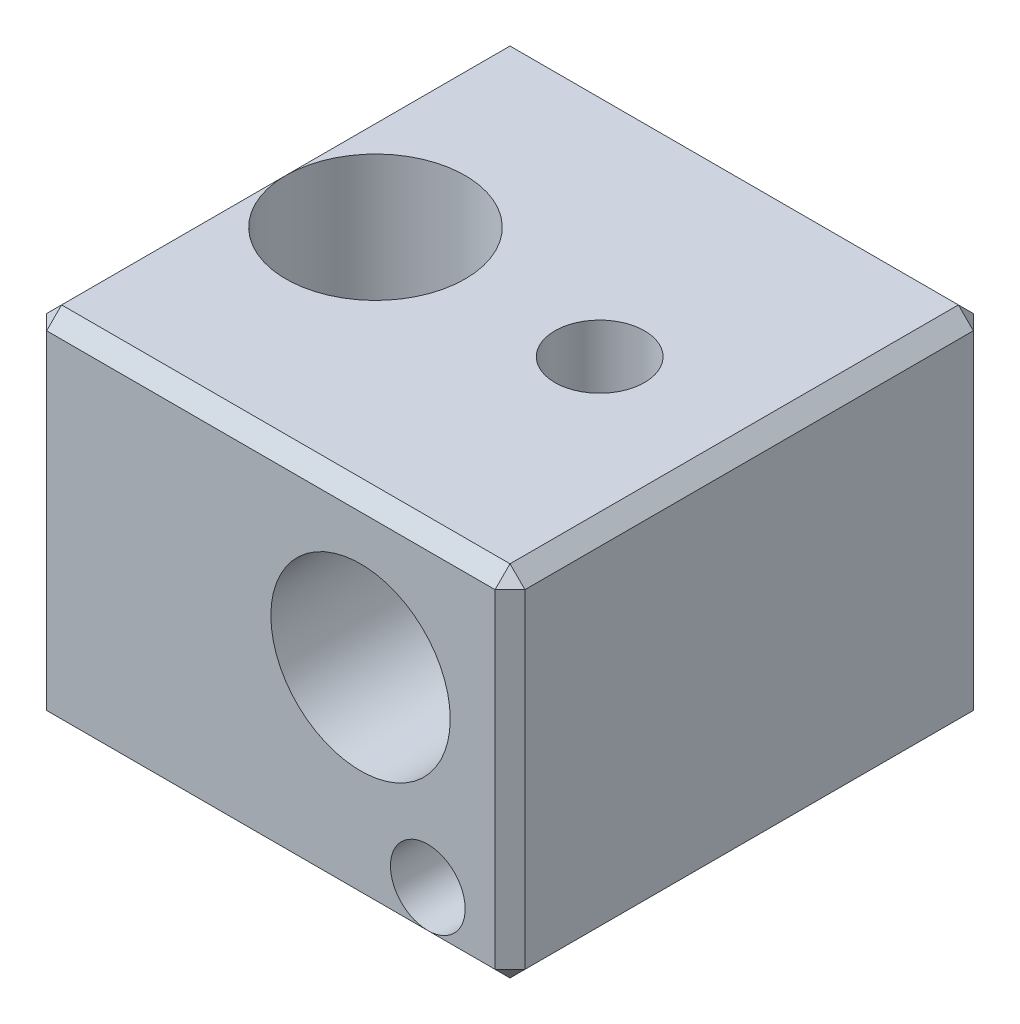
SolidWorks part; units mm, degrees
ref_plane "前基準面" through (0, 0, 0) normal (0, 0, 1) x (1, 0, 0)
ref_plane "上基準面" through (0, 0, 0) normal (0, 1, 0) x (1, 0, 0)
ref_plane "右基準面" through (0, 0, 0) normal (1, 0, 0) x (0, 0, -1)
sketch "草圖1" plane through (0, 0, 0) normal (0, 1, 0) x (1, 0, 0)
  line L0 (-8, 8) -> (8, -8) construction
  line L1 (-8, 8) -> (8, 8)
  line L2 (-8, 8) -> (-8, -8)
  line L3 (-8, -8) -> (8, -8)
  line L4 (8, 8) -> (8, -8)
  dimension "D1" = 16
  dimension "D2" = 16
extrude "填料-伸長1" add sketch "草圖1" along normal blind 12
sketch "草圖2" plane through (0, 12, 0) normal (0, 1, 0) x (1, 0, 0)
  line L1 (-8, 8) -> (-8, -8) construction
  circle A0 centre (-4.5, 0) radius 3
  dimension "D1" = 3.5
  dimension "D2" = 6
extrude "除料-伸長2" cut sketch "草圖2" against normal through all
sketch "草圖3" plane through (0, 0, 8) normal (0, 0, 1) x (1, 0, 0)
  line L0 (8, 12) -> (8, 0) construction
  line L1 (-8, 0) -> (8, 0) construction
  circle A0 centre (5.25, 1.75) radius 1.25
  dimension "D1" = 2.5
  dimension "D3" = 1.75
  dimension "D2" = 2.75
extrude "除料-伸長3" cut sketch "草圖3" against normal through all
sketch "草圖4" plane through (0, 0, 8) normal (0, 0, 1) x (1, 0, 0)
  line L0 (8, 12) -> (8, 0) construction
  line L1 (-8, 12) -> (8, 12) construction
  circle A0 centre (3, 7) radius 3
  dimension "D1" = 6
  dimension "D2" = 5
  dimension "D3" = 5
extrude "除料-伸長4" cut sketch "草圖4" against normal through all
chamfer "導角1" distance 0.5 angle 45 12 edges at (8, 12, 0) (0, 12, -8) (-8, 12, 0) (0, 12, 8) (-8, 0, 0) (0, 0, -8) (0, 0, 8) (8, 0, 0) (8, 6, -8) (-8, 6, -8) (8, 6, 8) (-8, 6, 8)
sketch "草圖5" plane through (0, 12, 0) normal (0, 1, 0) x (1, 0, 0)
  line L0 (0, -8) -> (6, -8) construction
  line L1 (0, -8) -> (6, -8) construction
  line L2 (3, -8) -> (3, 0) construction
  line L3 (3, 0) -> (0, 0) construction
  circle A0 centre (3, 0) radius 1.5
  dimension "D1" = 3
extrude "除料-伸長5" cut sketch "草圖5" against normal up to next
